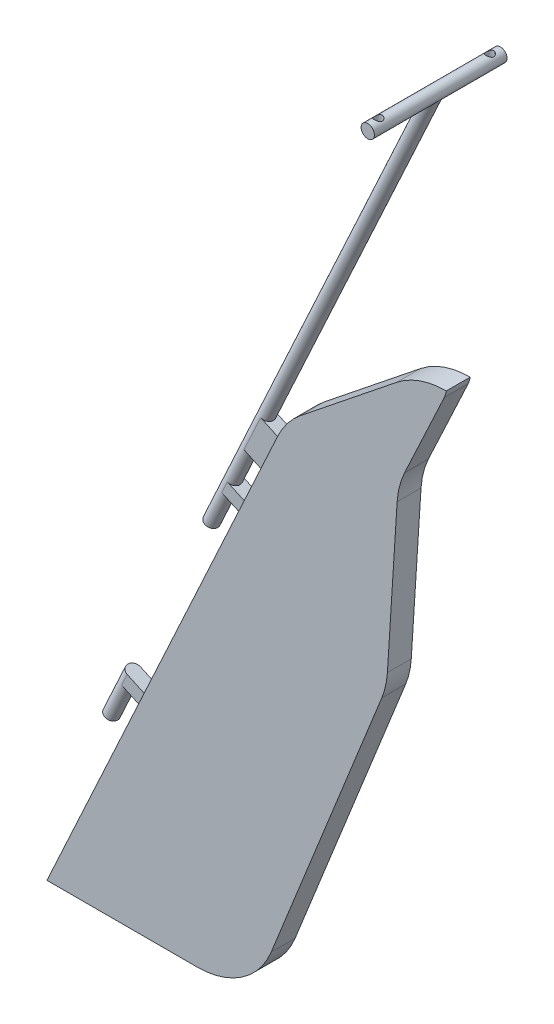
SolidWorks part; units mm, degrees
ref_plane "Plan de face" through (0, 0, 0) normal (0, 0, 1) x (1, 0, 0)
ref_plane "Plan de dessus" through (0, 0, 0) normal (0, 1, 0) x (1, 0, 0)
ref_plane "Plan de droite" through (0, 0, 0) normal (1, 0, 0) x (0, 0, -1)
sketch "Esquisse1" plane through (0, 0, 0) normal (0, 0, 1) x (1, 0, 0)
  line L0 (0, 0) -> (90, 195)
  line L1 (90, 195) -> (140, 235)
  line L3 (76.9505, 0) -> (0, 0)
  line L4 (140, 235) -> (150.9326, 235)
  line L5 (150.9326, 235) -> (132.3394, 195.2011)
  line L6 (132.3394, 195.2011) -> (127.9972, 127.139)
  line L7 (127.9972, 127.139) -> (76.9505, 0)
  point P3 (180.1654, 250)
  point P9 (172.5815, 250)
  point P10 (135.0233, 191.5088)
  point P11 (127.9972, 127.139)
  point P12 (76.9505, 0)
  point P13 (154.4253, 235)
  point P14 (150.9326, 235)
  point P15 (132.3394, 195.2011)
  dimension "D1" = 195
  dimension "D2" = 90
  dimension "D3" = 40
  dimension "D4" = 50
extrude "Boss.-Extru.1" add sketch "Esquisse1" along normal blind 9
sketch "Esquisse36" plane through (0, 0, 0) normal (-0.908, 0.4191, 0) x (0, 0, 1)
  line L0 (9, 214.7673) -> (9, 0) construction
  line L1 (7, 174.7673) -> (2, 174.7673)
  line L2 (7, 174.7673) -> (7, 169.7673)
  line L3 (7, 169.7673) -> (2, 169.7673)
  line L4 (2, 174.7673) -> (2, 169.7673)
  line L5 (7, 84.7673) -> (2, 84.7673)
  line L6 (7, 84.7673) -> (7, 79.7673)
  line L7 (7, 79.7673) -> (2, 79.7673)
  line L8 (2, 84.7673) -> (2, 79.7673)
  line L9 (9, 214.7673) -> (0, 214.7673) construction
  line L10 (7, 204.7673) -> (2, 204.7673)
  line L11 (7, 204.7673) -> (7, 189.7673)
  line L12 (7, 189.7673) -> (2, 189.7673)
  line L13 (2, 204.7673) -> (2, 189.7673)
  point P12 (4.5, 214.7673)
  dimension "D1" = 5
  dimension "D2" = 5
  dimension "D3" = 2
  dimension "D4" = 5
  dimension "D5" = 5
  dimension "D6" = 2
  dimension "D7" = 40
  dimension "D8" = 130
  dimension "D9" = 5
  dimension "D10" = 15
  dimension "D11" = 2
  dimension "D12" = 10
extrude "Boss.-Extru.4" add sketch "Esquisse36" along normal blind 8
sketch "Esquisse37" plane through (-7.2637, 3.3525, 0) normal (-0.908, 0.4191, 0) x (0, 0, 1)
  line L0 (4.5, 354.7673) -> (4.5, 154.7673)
  line L2 (2, 169.7673) -> (7, 169.7673) construction
  line L3 (7, 204.7673) -> (2, 204.7673) construction
  line L4 (7, 174.7673) -> (2, 174.7673) construction
  line L5 (7, 204.7673) -> (2, 204.7673) construction
  point P2 (4.2179, 202.2106)
  point P3 (4.4551, 153.3909)
  point P5 (7.4345, 400.7647)
  point P7 (4.5, 169.7673)
  point P10 (4.5, 204.7673)
  dimension "D1" = 20
  dimension "D2" = 150
sweep "Balayage2" add path "Esquisse37" circular profile diameter 5 parameters "D3"=5
sketch "Esquisse50" plane through (-7.2637, 3.3525, 0) normal (-0.908, 0.4191, 0) x (0, 0, 1)
  line L0 (4.5, 84.7673) -> (4.5, 64.7673)
  line L1 (7, 84.7673) -> (2, 84.7673) construction
  line L3 (2, 79.7673) -> (7, 79.7673) construction
  point P7 (4.5, 79.7673)
  dimension "D1" = 20
sweep "Balayage3" add path "Esquisse50" circular profile diameter 5 parameters "D3"=5
fillet "Congé2" radius 30 5 edges at (90, 195, 4.5) (140, 235, 4.5) (132.3394, 195.2011, 4.5) (127.9972, 127.139, 4.5) (76.9505, 0, 4.5)
fillet "Congé3" radius 10 1 edges at (150.9326, 235, 4.5)
sketch "Esquisse88" plane through (148.6681, 322.1143, 0) normal (0.4191, 0.908, 0) x (0.908, -0.4191, 0)
  line L0 (-8, 20.5) -> (-8, -29.5)
  circle A0 centre (-8, -4.5) radius 2.5 construction
  point P2 (-9.6991, -11.9301)
  point P3 (-8, -4.5)
  point P8 (-8, -13.0986)
  dimension "D1" = 50
sweep "Balayage4" add path "Esquisse88" circular profile diameter 5 parameters "D3"=5
sketch "Esquisse103" plane through (0, 0, 0) normal (0, 1, 0) x (1, 0, 0)
  line L0 (141.4045, -29.5) -> (141.4045, 20.5) construction
  line L1 (138.9045, -29.5) -> (143.9045, -29.5) construction
  line L2 (143.9045, 20.5) -> (138.9045, 20.5) construction
  circle A0 centre (141.4045, 16.5) radius 1.5
  circle A1 centre (141.3919, -25.5) radius 1.5
  dimension "D1" = 3
  dimension "D3" = 3
  dimension "D2" = 4
  dimension "D4" = 4
extrude "Enlèv. mat.-Extru.2" cut sketch "Esquisse103" against normal blind 10 and the other way through all
